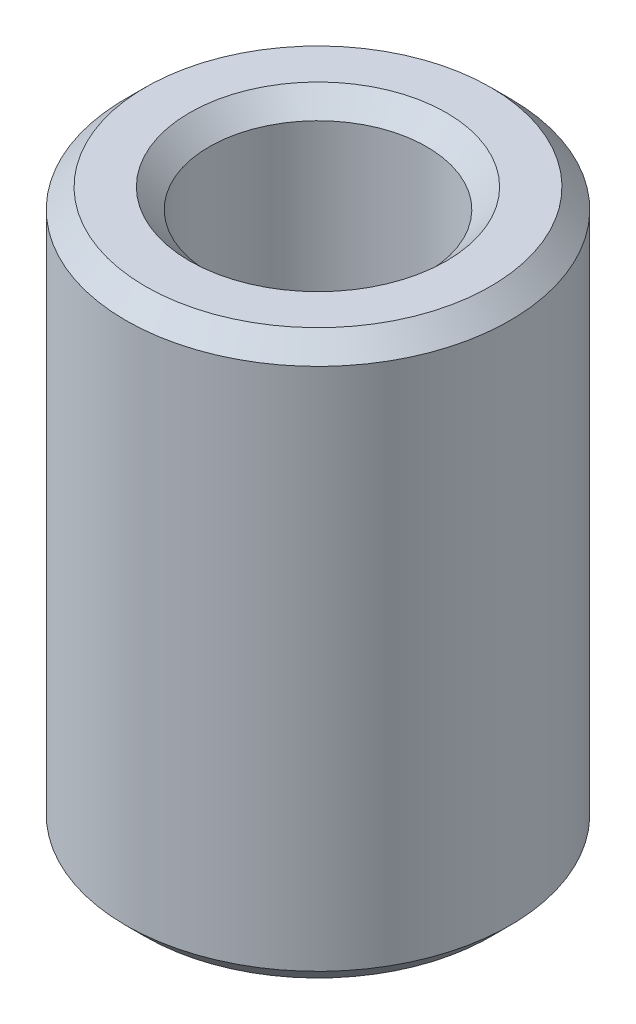
SolidWorks part; units mm, degrees
ref_plane "Front Plane" through (0, 0, 0) normal (0, 0, 1) x (1, 0, 0)
ref_plane "Top Plane" through (0, 0, 0) normal (0, 1, 0) x (1, 0, 0)
ref_plane "Right Plane" through (0, 0, 0) normal (1, 0, 0) x (0, 0, -1)
sketch "Sketch1" plane through (0, 0, 0) normal (0, 1, 0) x (1, 0, 0)
  circle A0 centre (0, 0) radius 27.5
  dimension "SLEEVE_OD" = 55
extrude "Boss-Extrude1" add sketch "Sketch1" along normal blind 80.5957
sketch "Sketch2" plane through (0, 0, 0) normal (0, 1, 0) x (1, 0, 0)
  circle A0 centre (0, 0) radius 15.5656
  dimension "BORE_D" = 31.1311
extrude "Cut-Extrude1" cut sketch "Sketch2" along normal through all
chamfer "Chamfer1" distance 2.8127 angle 45 4 edges at (0, 80.5957, 15.5656) (0, 0, 15.5656) (0, 0, 27.5) (0, 80.5957, 27.5)
